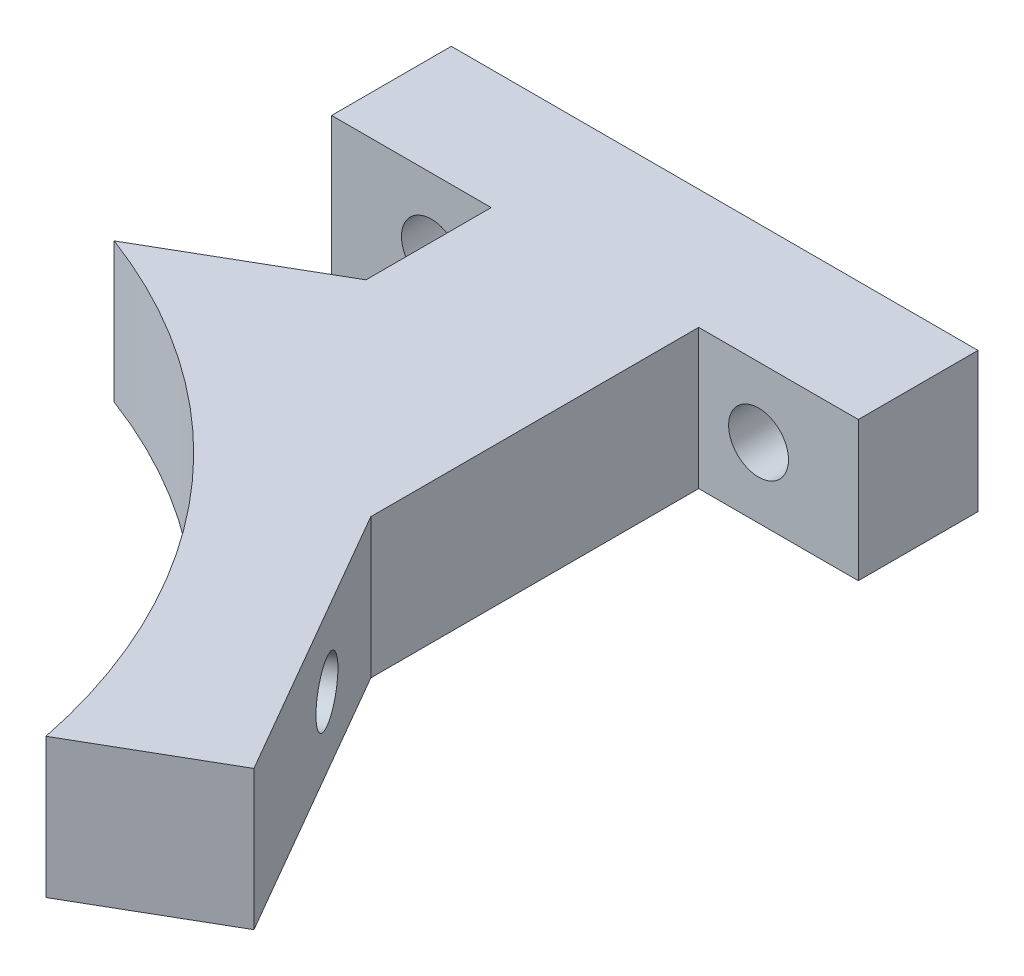
SolidWorks part; units mm, degrees
ref_plane "Front Plane" through (0, 0, 0) normal (0, 0, 1) x (1, 0, 0)
ref_plane "Top Plane" through (0, 0, 0) normal (0, 1, 0) x (1, 0, 0)
ref_plane "Right Plane" through (0, 0, 0) normal (1, 0, 0) x (0, 0, -1)
sketch "Sketch1" plane through (0, 0, 0) normal (0, 1, 0) x (1, 0, 0)
  line L0 (0, -46.3839) -> (25.6451, -46.3839) construction
  line L1 (0, 46.3839) -> (25.6458, 46.3839) construction
  line L2 (0, 0) -> (0, 46.3839) construction
  line L3 (0, 0) -> (0, -46.3839) construction
  line L4 (0, 0) -> (27.2798, 15.75) construction
  line L5 (27.2798, 15.75) -> (-27.2798, 15.75) construction
  line L6 (-27.2798, 15.75) -> (0, 0) construction
  circle A0 centre (0, 0) radius 31.5
  dimension "D1" = 63
  dimension "D2" = 46.3839
  dimension "D3" = 25.6458
  dimension "D4" = 60
extrude "Boss-Extrude1" add sketch "Sketch1" against normal mid plane 7
ref_plane "Plane1" through (27.2798, 0, -15.75) normal (0.866, 0, -0.5) x (-0.5, 0, -0.866)
sketch "Sketch2" plane through (27.2798, 0, -15.75) normal (0.866, 0, -0.5) x (-0.5, 0, -0.866)
  circle A0 centre (0, 0) radius 1.5
  dimension "D1" = 3
extrude "Cut-Extrude1" cut sketch "Sketch2" against normal blind 4
ref_axis "Axis1" through (0, -3.5, 0) along (0, 1, 0)
pattern_circular "CirPattern1" count 6 over 360 about axis through (0, -3.5, 0) along (0, 1, 0) of "Cut-Extrude1"
sketch "Sketch3" plane through (27.2798, 0, -15.75) normal (0.866, 0, -0.5) x (-0.5, 0, -0.866)
  line L0 (-31.5, -3.5) -> (31.5, -3.5) construction
  line L1 (20, -3.5) -> (-10, -3.5)
  line L2 (20, -3.5) -> (20, 3.5)
  line L3 (20, 3.5) -> (-10, 3.5)
  line L4 (-10, -3.5) -> (-10, 3.5)
  line L5 (31.5, 3.5) -> (-31.5, 3.5) construction
  circle A0 centre (0, 0) radius 1.5
  dimension "D3" = 3
  dimension "D1" = 10
  dimension "D2" = 20
extrude "Boss-Extrude2" add sketch "Sketch3" along normal blind 6 and the other way up to surface separate body other way up to face at (26.5204, -0.3431, 16.9977)
ref_plane "Plane2" through (0, 0, -46.3839) normal (0, 0, 1) x (1, 0, 0)
sketch "Sketch5" plane through (32.476, 0, -18.75) normal (0.866, 0, -0.5) x (-0.5, 0, -0.866)
  line L0 (6, -3.5) -> (6, 3.5) construction
  line L1 (-10, -3.5) -> (20, -3.5) construction
  line L2 (20, 3.5) -> (-10, 3.5) construction
  dimension "D1" = 6
sketch "Sketch6" plane through (0, 0, -46.3839) normal (0, 0, 1) x (1, 0, 0)
  line L0 (37.476, 0) -> (11.0758, 0) construction
  line L1 (11.0758, -3.5) -> (37.476, -3.5)
  line L2 (11.0758, -3.5) -> (11.0758, 3.5)
  line L3 (11.0758, 3.5) -> (37.476, 3.5)
  line L4 (37.476, -3.5) -> (37.476, 3.5)
  circle A0 centre (32.476, 0) radius 1.5
  circle A1 centre (16.0758, 0) radius 1.5
  dimension "D1" = 3
  dimension "D2" = 5
  dimension "D3" = 5
extrude "Boss-Extrude3" add sketch "Sketch6" along normal blind 6 separate body
sketch "Sketch7" plane through (0, 0, -40.3839) normal (0, 0, 1) x (1, 0, 0)
  line L0 (11.0758, -3.5) -> (37.476, -3.5) construction
  line L1 (29.476, 3.5) -> (19.0758, 3.5)
  line L2 (29.476, 3.5) -> (29.476, -3.5)
  line L3 (29.476, -3.5) -> (19.0758, -3.5)
  line L4 (19.0758, 3.5) -> (19.0758, -3.5)
  circle A0 centre (32.476, 0) radius 1.5 construction
  circle A1 centre (16.0758, 0) radius 1.5 construction
  dimension "D1" = 3
  dimension "D2" = 3
extrude "Boss-Extrude4" add sketch "Sketch7" along normal up to next
delete or keep bodies "Body-Delete/Keep 2" type delete bodies bodies 103
